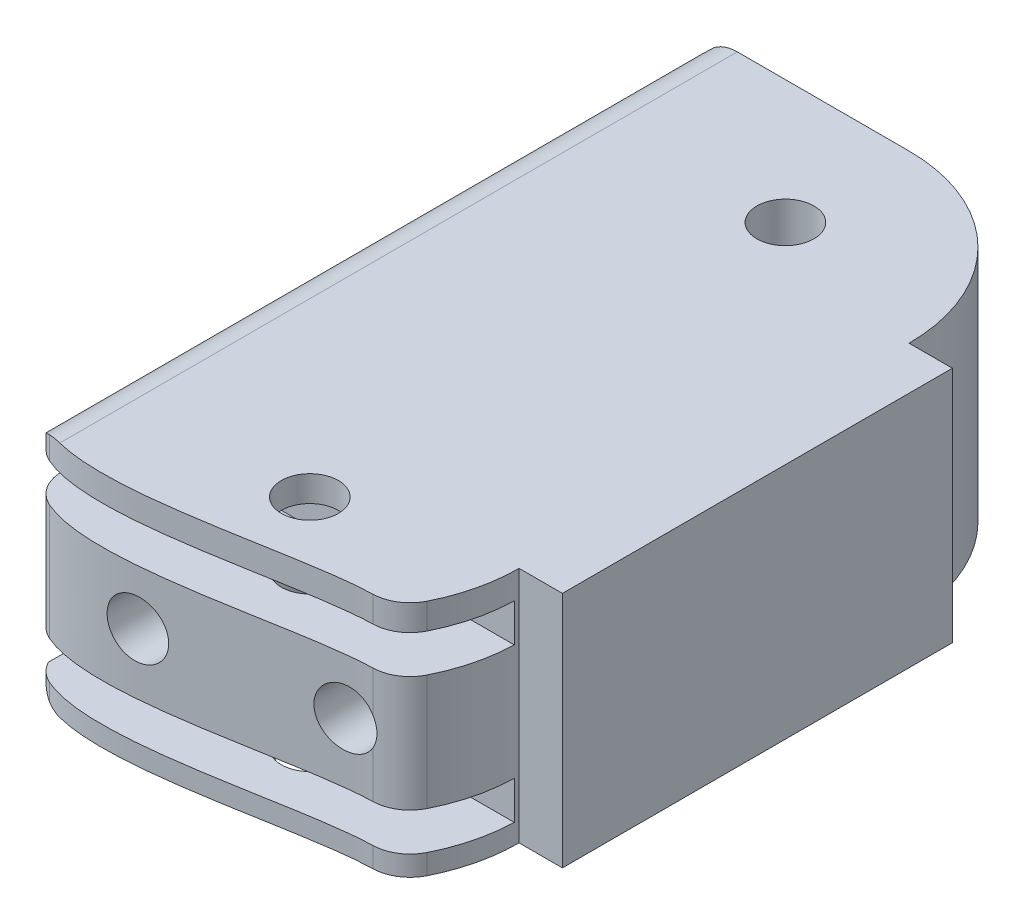
SolidWorks part; units mm, degrees
ref_plane "Front Plane" through (0, 0, 0) normal (0, 0, 1) x (1, 0, 0)
ref_plane "Top Plane" through (0, 0, 0) normal (0, 1, 0) x (1, 0, 0)
ref_plane "Right Plane" through (0, 0, 0) normal (1, 0, 0) x (0, 0, -1)
sketch "Sketch1" plane through (0, 0, 0) normal (0, 0, 1) x (1, 0, 0)
  line L0 (-24.2561, -24.0702) -> (-22.0061, -24.0702) construction
  line L1 (-24.2561, -17.8202) -> (-2.2017, -17.8202)
  line L2 (-24.2561, -17.8202) -> (-24.2561, -30.3202)
  line L3 (-24.2561, -30.3202) -> (-2.2017, -30.3202)
  line L4 (-2.2017, -17.8202) -> (-2.2017, -30.3202)
  line L5 (-2.2017, -24.0702) -> (-4.4517, -24.0702) construction
  line L6 (-22.0061, -24.0702) -> (-22.0061, -30.3202) construction
  line L7 (-4.4517, -24.0702) -> (-4.4517, -30.3202) construction
extrude "Boss-Extrude1" add sketch "Sketch1" along normal blind 40
sketch "Sketch2" plane through (0, -30.3202, 0) normal (0, -1, 0) x (1, 0, 0)
  line L0 (-4.4789, 29.25) -> (-2.2017, 29.25)
  line L1 (-24.2561, 0) -> (-2.2017, 0) construction
  line L2 (-13.2289, 0) -> (-13.2289, 8.75) construction
  line L4 (-24.2561, 40) -> (-24.2561, 0) construction
  line L5 (-4.4789, 8.75) -> (-2.2017, 8.75)
  line L6 (-2.2017, 40) -> (-2.2017, 0) construction
  line L7 (-13.2289, 40) -> (-13.2289, 29.25) construction
  line L8 (-24.2561, 40) -> (-2.2017, 40) construction
  line L10 (-13.2289, 29.25) -> (-13.2289, 31.5) construction
  line L11 (-13.2289, 8.75) -> (-13.2289, 6.5) construction
  line L12 (-24.2561, 0) -> (-2.2017, 0) construction
  arc A1 (-13.2289, 0) -> (-4.4789, 8.75) centre (-13.2289, 8.75) ccw
  circle A4 centre (-13.2289, 6.5) radius 1.5
  circle A5 centre (-13.2289, 31.5) radius 1.5
  arc A6 (-4.4789, 29.25) -> (-6.1039, 34.329) centre (-13.2289, 29.25) ccw
  spline S0 degree 3 poles (-2.2017, 8.75) (5.3921, 3.8803) (-0.7771, -4.5233) (-17.1743, -10.6233) (-34.8214, -0.026) (-24.2561, 8.75) knots 0 0 0 0 0.283273 0.504245 1 1 1 1
  spline S1 degree 3 poles (-24.2561, 29.25) (-34.2779, 38.4171) (-13.2275, 50.308) (7.8404, 38.417) (-2.2017, 29.25) knots 0 0 0 0 0.499862 1 1 1 1
  spline S2 degree 1 poles (-13.2289, 0) (-23.4906, 0) knots 0 0 1 1
  spline S3 degree 2 poles (-23.4906, 0) (-24.9665, 4.2378) (-24.2561, 8.75) knots 0 0 0 1 1 1
  spline S4 degree 3 poles (-6.1039, 34.329) (-10.7206, 33.5272) (-28.6414, 40.8452) (-24.2561, 29.25) knots 0 0 0 0 1 1 1 1
extrude "Cut-Extrude1" cut sketch "Sketch2" against normal blind 15 and the other way blind 10
fillet "Fillet3" radius 2 4 edges at (-24.2561, -17.8202, 18.7439) (-24.2561, -30.3202, 18.7439) (-24.2561, -24.0702, 3.0015) (-24.2561, -24.0702, 34.4864)
ref_plane "Plane1" through (0, 0, 0) normal (0, 0, 1) x (1, 0, 0)
sketch "Sketch5" plane through (0, 0, 0) normal (0, 0, 1) x (1, 0, 0)
  line L0 (-2.2017, -24.0702) -> (-8.4468, -24.0702) construction
  line L1 (-2.2017, -30.3202) -> (-24.2561, -30.3202) construction
  line L2 (-2.2017, -30.3202) -> (-2.2017, -17.8202) construction
  line L3 (-2.2017, -17.8202) -> (-24.2561, -17.8202) construction
  line L4 (-24.2561, -30.3202) -> (-24.2561, -17.8202) construction
  line L5 (-24.2561, -24.0702) -> (-18.0111, -24.0702) construction
  circle A0 centre (-18.0111, -24.0702) radius 1.5
  circle A1 centre (-8.4468, -24.0702) radius 1.5
extrude "Cut-Extrude4" cut sketch "Sketch5" along normal through all
ref_plane "Plane5" through (0, 0, 38) normal (0, 0, 1) x (1, 0, 0)
sketch "Sketch16" plane through (0, 0, 38) normal (0, 0, 1) x (1, 0, 0)
  line L0 (-2.2017, -17.681) -> (-2.2017, -19.181) construction
  line L1 (-2.2017, -17.681) -> (-24.2561, -17.681) construction
  line L2 (-2.2017, -17.681) -> (-2.2017, -30.7619) construction
  line L3 (-2.2017, -30.7619) -> (-24.2561, -30.7619) construction
  line L4 (-24.2561, -17.681) -> (-24.2561, -30.7619) construction
  line L5 (-2.2017, -17.681) -> (-24.2561, -30.7619) construction
  line L6 (-2.2017, -30.7619) -> (-24.2561, -17.681) construction
  line L7 (-2.2017, -30.7619) -> (-2.2017, -29.2619) construction
  line L9 (-2.2017, -19.181) -> (-24.2561, -19.181)
  line L10 (-2.2017, -19.181) -> (-2.2017, -21.181)
  line L11 (-2.2017, -21.181) -> (-24.2561, -21.181)
  line L12 (-24.2561, -19.181) -> (-24.2561, -21.181)
  line L13 (-2.2017, -19.181) -> (-24.2561, -21.181) construction
  line L14 (-2.2017, -21.181) -> (-24.2561, -19.181) construction
  line L15 (-2.2017, -29.2619) -> (-24.2561, -29.2619)
  line L16 (-2.2017, -29.2619) -> (-2.2017, -27.2619)
  line L17 (-2.2017, -27.2619) -> (-24.2561, -27.2619)
  line L18 (-24.2561, -29.2619) -> (-24.2561, -27.2619)
  line L19 (-2.2017, -29.2619) -> (-24.2561, -27.2619) construction
  line L20 (-2.2017, -27.2619) -> (-24.2561, -29.2619) construction
  point P4 (-13.2289, -24.2214)
  point P10 (-13.2289, -20.181)
  point P14 (-13.2289, -28.2619)
extrude "Cut-Extrude6" cut sketch "Sketch16" against normal blind 8.5
fillet "Fillet4" radius 2 3 edges at (-6.1039, -18.5006, 34.329) (-6.1039, -24.2214, 34.329) (-6.1039, -29.7911, 34.329)
